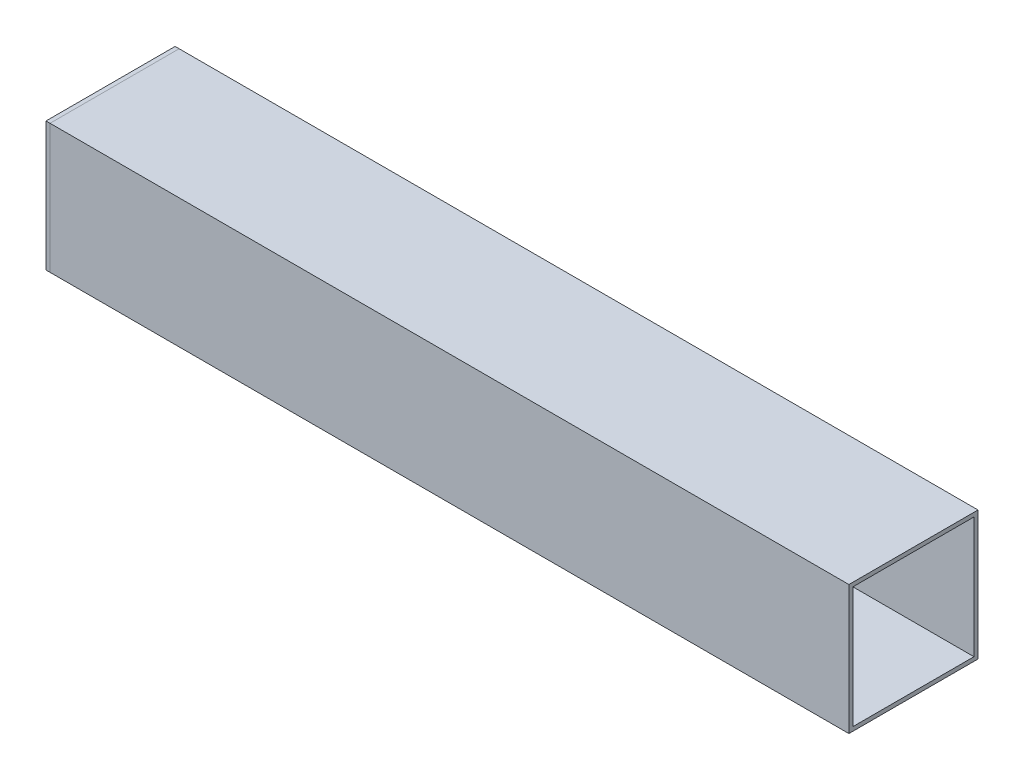
SolidWorks part; units mm, degrees
ref_plane "Front Plane" through (0, 0, 0) normal (0, 0, 1) x (1, 0, 0)
ref_plane "Top Plane" through (0, 0, 0) normal (0, 1, 0) x (1, 0, 0)
ref_plane "Right Plane" through (0, 0, 0) normal (1, 0, 0) x (0, 0, -1)
sketch "Sketch1" plane through (0, 0, 0) normal (1, 0, 0) x (0, 0, -1)
  line L0 (-98.425, 3.175) -> (-98.425, 98.425)
  line L1 (0, 0) -> (-101.6, 0)
  line L2 (0, 0) -> (0, 101.6)
  line L3 (0, 101.6) -> (-101.6, 101.6)
  line L4 (-101.6, 0) -> (-101.6, 101.6)
  line L5 (-3.175, 98.425) -> (-98.425, 98.425)
  line L6 (-3.175, 3.175) -> (-3.175, 98.425)
  line L7 (-3.175, 3.175) -> (-98.425, 3.175)
  dimension "D1" = 101.6
  dimension "D2" = 101.6
  dimension "D3" = 3.175
extrude "Boss-Extrude1" add sketch "Sketch1" along normal blind 628.65
sketch "Sketch2" plane through (0, 0, 0) normal (-1, 0, 0) x (0, 0, 1)
  line L4 (0, 101.6) -> (0, 0)
  line L5 (0, 0) -> (101.6, 0)
  line L6 (101.6, 0) -> (101.6, 101.6)
  line L7 (101.6, 101.6) -> (0, 101.6)
  line L8 (0, 101.6) -> (0, 0)
  line L9 (0, 0) -> (101.6, 0)
  line L10 (101.6, 0) -> (101.6, 101.6)
  line L11 (101.6, 101.6) -> (0, 101.6)
  dimension "D1" = 0
extrude "Boss-Extrude2" add sketch "Sketch2" along normal blind 3.175 separate body
